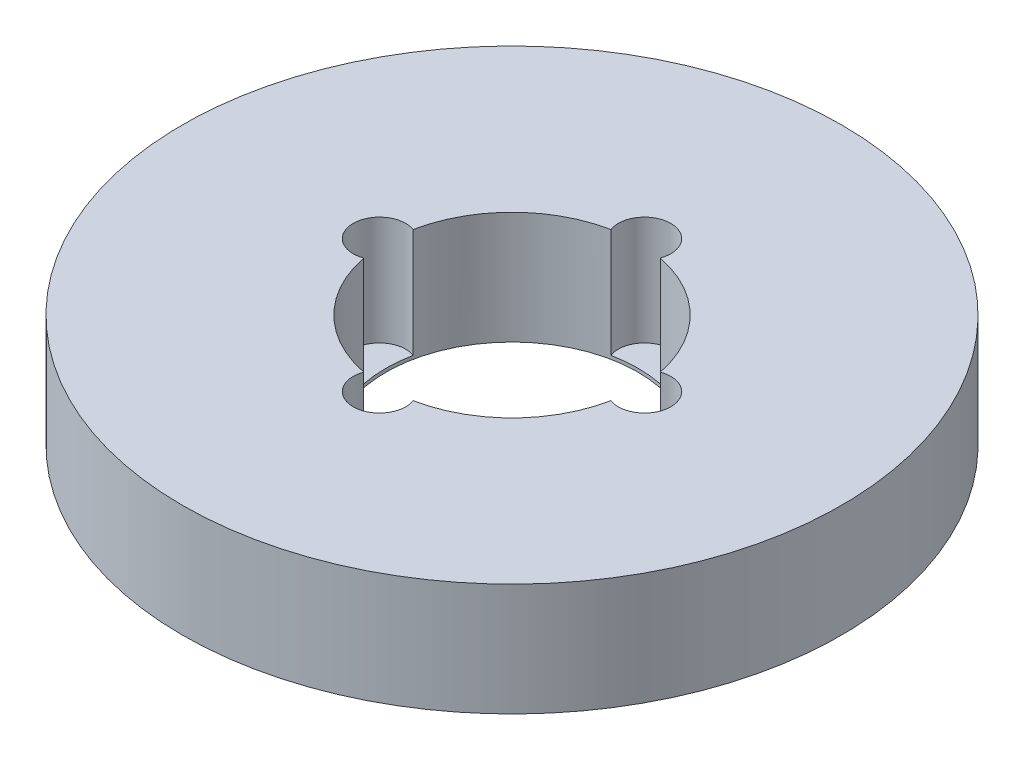
SolidWorks part; units mm, degrees
ref_plane "Front Plane" through (0, 0, 0) normal (0, 0, 1) x (1, 0, 0)
ref_plane "Top Plane" through (0, 0, 0) normal (0, 1, 0) x (1, 0, 0)
ref_plane "Right Plane" through (0, 0, 0) normal (1, 0, 0) x (0, 0, -1)
sketch "Sketch1" plane through (0, 0, 0) normal (0, 1, 0) x (1, 0, 0)
  circle A0 centre (0, 0) radius 85
  dimension "FLANGE_OD" = 170
extrude "Boss-Extrude1" add sketch "Sketch1" along normal blind 29
sketch "Sketch2" plane through (0, 0, 0) normal (0, 1, 0) x (1, 0, 0)
  circle A0 centre (0, 0) radius 32.5
  dimension "BORE_D" = 65
extrude "Cut-Extrude1" cut sketch "Sketch2" along normal through all
sketch "Sketch3" plane through (0, 29, 0) normal (0, 1, 0) x (1, 0, 0)
  circle A0 centre (0, 0) radius 34.1803 construction
  circle A1 centre (-34.1803, 0) radius 6.7834
  dimension "BOLT_D" = 13.5669
  dimension "BOLT_PCD" = 68.3606
extrude "Cut-Extrude2" cut sketch "Sketch3" against normal blind 28.1108
pattern_circular "CirPattern1" count 4 over 360 about axis through (0, 0, 0) along (0, 1, 0) of "Cut-Extrude2"
